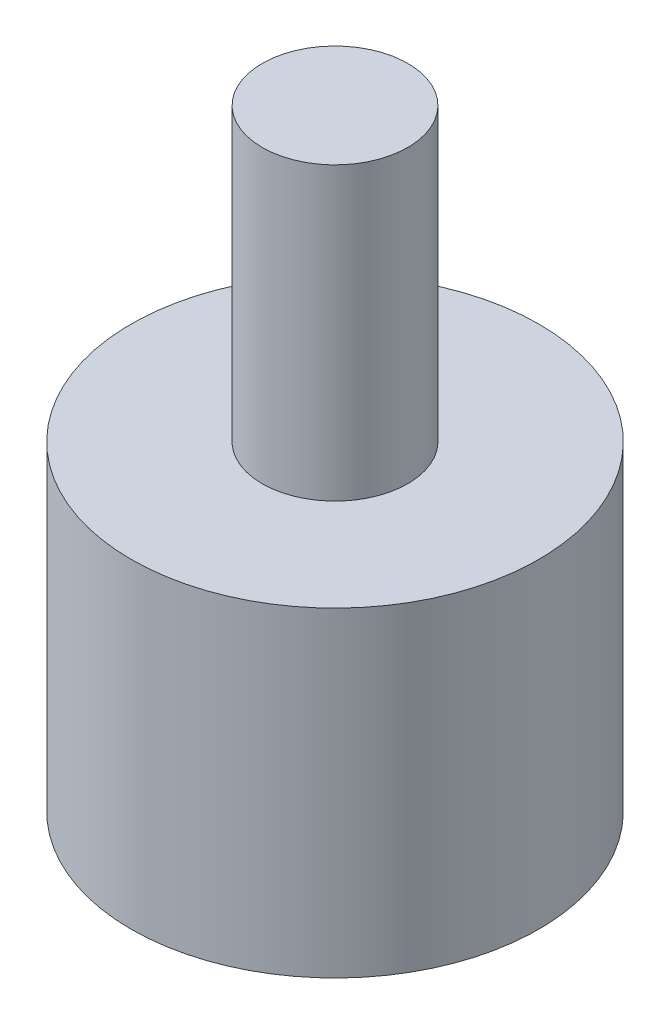
SolidWorks part; units mm, degrees
ref_plane "Ebene vorne" through (0, 0, 0) normal (0, 0, 1) x (1, 0, 0)
ref_plane "Ebene oben" through (0, 0, 0) normal (0, 1, 0) x (1, 0, 0)
ref_plane "Ebene rechts" through (0, 0, 0) normal (1, 0, 0) x (0, 0, -1)
sketch "Skizze1" plane through (0, 0, 0) normal (1, 0, 0) x (0, 0, -1)
  line L0 (-190, 212) -> (-190, 243.7464) construction
  line L1 (-190, 212) -> (-187, 212)
  line L2 (-187, 212) -> (-187, 206)
  line L3 (-187, 206) -> (-183, 206)
  line L4 (-183, 206) -> (-183, 217)
  line L5 (-183, 217) -> (-187.5, 217)
  line L6 (-187.5, 217) -> (-187.5, 227)
  line L7 (-187.5, 227) -> (-190, 227)
  line L9 (-190, 227) -> (-190, 212)
  point P12 (0, 0)
  point P17 (-190, 227)
sketch "Skizze2" plane through (0, 0, 0) normal (1, 0, 0) x (0, 0, -1)
  line L0 (-190, 227) -> (-190, 212)
  line L1 (-190, 212) -> (-187, 212)
  line L2 (-187, 212) -> (-187, 206)
  line L3 (-187, 206) -> (-183, 206)
  line L4 (-183, 206) -> (-183, 217)
  line L5 (-183, 217) -> (-187.5, 217)
  line L6 (-187.5, 217) -> (-187.5, 227)
  line L7 (-187.5, 227) -> (-190, 227)
revolve "Rotation1" add sketch "Skizze2" angle 360 about L9
